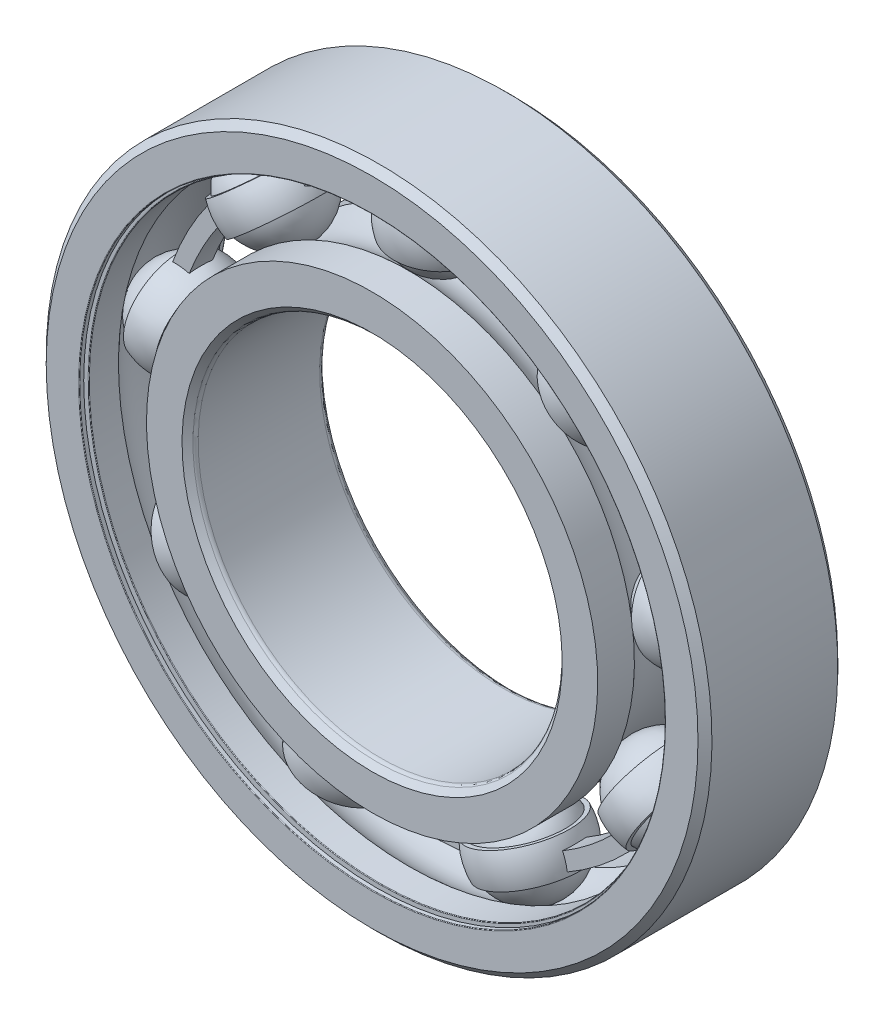
SolidWorks part; units mm, degrees
ref_plane "Front Plane" through (0, 0, 0) normal (0, 0, 1) x (1, 0, 0)
ref_plane "Top Plane" through (0, 0, 0) normal (0, 1, 0) x (1, 0, 0)
ref_plane "Right Plane" through (0, 0, 0) normal (1, 0, 0) x (0, 0, -1)
sketch "Sketch1" plane through (0, 0, 0) normal (0, 0, 1) x (1, 0, 0)
  line L0 (-50, 0) -> (50, 0) construction
  line L1 (-27.5, 0) -> (27.5, 0) construction
  circle A0 centre (0, 0) radius 27.5 construction
  circle A1 centre (0, 0) radius 50 construction
  point P3 (0, 0)
  point P6 (0, 0)
  point P7 (0, -27.5)
  point P11 (0, -50)
  point P12 (0, 27.5)
  point P13 (0, 50)
  dimension "OD" = 100
  dimension "ID" = 55
sketch "Sketch2" plane through (0, 0, 0) normal (1, 0, 0) x (0, 0, -1)
  line L0 (-10.5, 50) -> (10.5, 50) construction
  line L1 (0, 50) -> (0, -50) construction
  line L2 (9.45, 50) -> (-9.45, 50)
  line L3 (-9.45, 50) -> (-10.5, 48.95)
  line L4 (-10.5, 48.95) -> (-10.5, 43.6115)
  line L5 (-10.5, 43.6115) -> (-4.9875, 43.6115)
  line L6 (10.5, 43.6115) -> (4.9875, 43.6115)
  line L7 (10.5, 48.95) -> (10.5, 43.6115)
  line L8 (9.45, 50) -> (10.5, 48.95)
  line L9 (0, 50) -> (0, 38.75) construction
  line L10 (0, 38.75) -> (0, 27.5) construction
  line L11 (0, 50) -> (0, -50) construction
  line L12 (-10.5, 0) -> (10.5, 0) construction
  line L13 (10.5, 27.5) -> (-10.5, 27.5) construction
  line L14 (0, 45.7149) -> (0, 31.7851) construction
  line L15 (-10.5, -27.5) -> (10.5, -27.5) construction
  line L16 (-10.5, -27.5) -> (-10.5, 27.5) construction
  line L17 (10.5, 50) -> (10.5, -50) construction
  arc A0 (-4.9875, 43.6115) -> (4.9875, 43.6115) centre (0, 38.75) cw
  circle A1 centre (0, 38.75) radius 6.9649 construction
  point P14 (0, 27.5)
  point P17 (0, 0)
  point P21 (0, 50)
  point P29 (0, 27.5)
  point P30 (0, -27.5)
  point P35 (0, 45.7149)
  dimension "Approx. Ball Dia." = 13.9298
  dimension "Width" = 21
  dimension "D1" = 45
  dimension "D2" = 1.05
  dimension "D3" = 9.975
  dimension "D4" = 4.8615
  dimension "For Shaft Diameter" = 55
  dimension "For Housing ID" = 100
sketch "Sketch3" plane through (0, 0, 0) normal (1, 0, 0) x (0, 0, -1)
  line L0 (9.45, 50) -> (10.5, 48.95) construction
  line L1 (10.5, 48.95) -> (10.5, 43.6115) construction
  line L2 (10.5, 43.6115) -> (4.9875, 43.6115) construction
  line L3 (-10.5, 43.6115) -> (-4.9875, 43.6115) construction
  line L4 (-10.5, 48.95) -> (-10.5, 43.6115) construction
  line L5 (-9.45, 50) -> (-10.5, 48.95) construction
  line L6 (9.45, 50) -> (-9.45, 50) construction
  line L7 (9.45, 50) -> (10.5, 48.95)
  line L8 (10.5, 48.95) -> (10.5, 43.6115)
  line L9 (10.5, 43.6115) -> (4.9875, 43.6115)
  line L10 (-10.5, 43.6115) -> (-4.9875, 43.6115)
  line L11 (-10.5, 48.95) -> (-10.5, 43.6115)
  line L12 (-9.45, 50) -> (-10.5, 48.95)
  line L13 (9.45, 50) -> (-9.45, 50)
  arc A0 (4.9875, 43.6115) -> (-4.9875, 43.6115) centre (0, 38.75) ccw construction
  arc A1 (4.9875, 43.6115) -> (-4.9875, 43.6115) centre (0, 38.75) ccw
revolve "Revolve1" add sketch "Sketch3" angle 360 about L12
sketch "Sketch8" plane through (0, 0, 0) normal (1, 0, 0) x (0, 0, -1)
  line L0 (-10.5, 43.6115) -> (-4.9875, 43.6115) construction
  line L1 (-9.828, 43.6115) -> (-9.45, 43.6115)
  line L2 (-9.828, 43.6115) -> (-9.828, 45.741) construction
  line L3 (-9.828, 45.741) -> (-9.45, 45.741)
  line L4 (-9.45, 43.6115) -> (-9.45, 45.741)
  line L5 (10.5, 43.6115) -> (4.9875, 43.6115) construction
  line L6 (9.45, 43.6115) -> (9.828, 43.6115)
  line L7 (9.45, 43.6115) -> (9.45, 45.741)
  line L8 (9.45, 45.741) -> (9.828, 45.741)
  line L9 (9.828, 43.6115) -> (9.828, 45.741) construction
  line L10 (-9.45, 45.741) -> (9.45, 45.741) construction
  line L11 (0, 50) -> (0, -50) construction
  line L12 (-9.828, 45.741) -> (-9.828, 47.8705) construction
  line L13 (-9.828, 47.8705) -> (-9.828, 50) construction
  line L14 (-10.5, 50) -> (10.5, 50) construction
  line L15 (-9.828, 43.6115) -> (-10.5, 43.6115)
  line L16 (-10.5, 43.6115) -> (-10.5, 43.9895)
  line L17 (-10.5, 48.95) -> (-10.5, 43.6115) construction
  line L18 (-10.5, 43.9895) -> (-9.828, 43.9895)
  line L19 (-9.828, 43.9895) -> (-9.828, 45.741)
  line L20 (9.828, 43.6115) -> (10.5, 43.6115)
  line L21 (10.5, 43.6115) -> (10.5, 43.9895)
  line L22 (10.5, 48.95) -> (10.5, 43.6115) construction
  line L23 (10.5, 43.9895) -> (9.828, 43.9895)
  line L24 (9.828, 43.9895) -> (9.828, 45.741)
  point P12 (0, 45.741)
  dimension "D1" = 18.9
  dimension "D2" = 0.378
revolve "Cut-Revolve1" cut sketch "Sketch8" angle 360 about L12
sketch "Sketch4" plane through (0, 0, 0) normal (1, 0, 0) x (0, 0, -1)
  line L0 (0, 50) -> (0, -50) construction
  line L1 (0, 50) -> (0, -50) construction
  line L2 (-9.45, 27.5) -> (-10.5, 28.55)
  line L3 (-10.5, 28.55) -> (-10.5, 33.8885)
  line L5 (-10.5, 33.8885) -> (-4.9875, 33.8885)
  line L6 (-9.45, 27.5) -> (9.45, 27.5)
  line L8 (9.45, 27.5) -> (10.5, 28.55)
  line L10 (10.5, 28.55) -> (10.5, 33.8885)
  line L11 (10.5, 33.8885) -> (4.9875, 33.8885)
  line L12 (-10.5, 48.95) -> (-10.5, 43.6115) construction
  line L13 (9.45, 50) -> (10.5, 48.95) construction
  line L15 (10.5, -48.95) -> (10.5, 48.95) construction
  line L16 (9.45, 50) -> (9.45, -50) construction
  arc A1 (4.9875, 33.8885) -> (-4.9875, 33.8885) centre (0, 38.75) cw
  circle A2 centre (0, 38.75) radius 6.9649 construction
  point P1 (0, 27.5)
revolve "Revolve2" add sketch "Sketch4" angle 360 about L12
sketch "Sketch5" plane through (0, 0, 0) normal (1, 0, 0) x (0, 0, -1)
  line L0 (-6.9649, 38.75) -> (6.9649, 38.75)
  arc A2 (-6.9649, 38.75) -> (6.9649, 38.75) centre (0, 38.75) cw
  arc A3 (4.9875, 43.6115) -> (-4.9875, 43.6115) centre (0, 38.75) ccw construction
revolve "Revolve3" add sketch "Sketch5" angle 360 about L0
sketch "Sketch6" plane through (0, 0, 0) normal (1, 0, 0) x (0, 0, -1)
  line L0 (-4.9875, 43.6115) -> (-4.9875, 41.1808) construction
  line L1 (-4.9875, 41.1808) -> (-4.9875, 38.75) construction
  line L2 (-4.9875, 38.75) -> (-4.9875, 36.3192) construction
  line L3 (-4.9875, 36.3192) -> (-4.9875, 33.8885) construction
  line L4 (-10.5, 41.1808) -> (-9.8378, 41.1808) construction
  line L5 (-4.9875, 41.1808) -> (-4.9875, 36.3192) construction
  line L7 (-9.8378, 41.1808) -> (-9.1756, 41.1808) construction
  line L8 (-9.1756, 41.1808) -> (-8.5135, 41.1808) construction
  line L10 (0, 50) -> (0, -50) construction
  line L11 (0, 50) -> (0, -50) construction
  line L12 (-10.5, 43.6115) -> (-10.5, 41.1808) construction
  line L13 (-7.1891, 41.1808) -> (-6.5269, 41.1808) construction
  line L14 (-10.5, 48.95) -> (-10.5, -48.95) construction
  line L15 (-10.5, 41.1808) -> (-10.5, 38.75) construction
  line L16 (-10.5, 38.75) -> (-10.5, 36.3192) construction
  line L17 (-10.5, 36.3192) -> (-10.5, 33.8885) construction
  line L18 (-8.5135, 41.1808) -> (-7.8513, 41.1808) construction
  line L19 (-7.8513, 41.1808) -> (-7.1891, 41.1808) construction
  line L20 (-6.5269, 41.1808) -> (-7.1891, 41.1808)
  line L21 (-10.5, 36.3192) -> (-9.8378, 36.3192) construction
  line L22 (-9.8378, 36.3192) -> (-9.1756, 36.3192) construction
  line L23 (-9.1756, 36.3192) -> (-8.5135, 36.3192) construction
  line L24 (-8.5135, 36.3192) -> (-7.8513, 36.3192) construction
  line L25 (-7.8513, 36.3192) -> (-7.1891, 36.3192) construction
  line L26 (-7.1891, 36.3192) -> (-6.5269, 36.3192) construction
  line L27 (-6.5269, 36.3192) -> (-7.1891, 36.3192)
  line L28 (-7.8513, 41.1808) -> (-7.8513, 36.3192) construction
  line L30 (-7.5202, 41.1808) -> (-7.5202, 36.3192) construction
  circle A0 centre (0, 38.75) radius 6.9649 construction
  arc A2 (-7.1891, 36.3192) -> (-7.1891, 41.1808) centre (1.5684, 38.75) cw
  arc A3 (-6.5269, 41.1808) -> (-6.5269, 36.3192) centre (0, 38.75) ccw
revolve "Revolve4" add sketch "Sketch6" angle 360 about L11
sketch "Sketch7" plane through (0, 0, 0) normal (0, 0, 1) x (1, 0, 0)
  line L0 (-6.9649, 38.75) -> (6.9649, 38.75) construction
  line L1 (0, 31.7851) -> (0, 45.7149) construction
  line L2 (0, 0) -> (13.2533, 36.4131) construction
  line L8 (0, 50) -> (0, -50) construction
  line L9 (24.908, 29.6842) -> (26.4705, 31.5463)
  line L10 (0, 50) -> (0, -50) construction
  line L11 (0, 41.1808) -> (0, 38.75)
  arc A1 (24.908, 29.6842) -> (0, 38.75) centre (0, 0) ccw
  arc A2 (26.4705, 31.5463) -> (0, 41.1808) centre (0, 0) ccw
  dimension "D1" = 40
  dimension "D2" = 13.9298
extrude "Boss-Extrude1" add sketch "Sketch7" along normal mid plane 3.5
pattern_circular "CirPattern1" count 9 over 360 about axis through (0, 0, 10.5) along (0, 0, -1) of bodies 104 134
pattern_circular "CirPattern2" count 9 over 360 about axis through (0, 0, 10.5) along (0, 0, -1) of "Revolve4", "Boss-Extrude1" reverse direction yes
fillet "Fillet1" radius 0.0945 4 edges at (0, -43.6115, -9.45) (0, -43.9895, -10.5) (0, -43.6115, 9.45) (0, -43.9895, 10.5)
fillet "Fillet2" radius 0.7875 2 edges at (0, -27.5, -9.45) (0, -27.5, 9.45)
ref_plane "Plane1" through (13.2533, 36.4131, 0) normal (0.342, 0.9397, 0) x (0.9397, -0.342, 0)
sketch "Sketch9" plane through (13.2533, 36.4131, 0) normal (0.342, 0.9397, 0) x (0.9397, -0.342, 0)
  line L0 (-6.7084, -1.75) -> (-6.7084, -5.25)
  line L1 (-6.7084, -5.25) -> (-2.9099, -5.25)
  line L2 (-2.9099, -5.25) -> (0, -2.8083)
  line L3 (0, -2.8083) -> (2.9099, -5.25)
  line L4 (2.9099, -5.25) -> (6.7084, -5.25)
  line L5 (6.7084, -5.25) -> (6.7084, -1.75)
  line L6 (6.7084, -1.75) -> (-6.7084, -1.75)
  line L7 (0, -1.75) -> (0, 0) construction
  line L8 (-6.7084, -1.75) -> (-6.7084, 0) construction
  dimension "D1" = 3.5
  dimension "D2" = 1.75
  dimension "D3" = 40
extrude "Boss-Extrude2" [suppressed] add sketch "Sketch9" along normal blind 6.0943 draft 15 and the other way blind 6.0943 draft 10 separate body draft outward yes other way draft outward yes
fillet "Fillet3" [suppressed] radius 1.05
mirror "Mirror1" [suppressed] about plane through (0, 0, 0) normal (0, 0, 1) of bodies 149
pattern_circular "CirPattern3" [suppressed] count 9 over 360 about axis through (0, 0, 10.5) along (0, 0, -1) of bodies 158 149
equation "\"D2@Sketch2\" = \"Width@Sketch2\" * .05"
equation "\"D3@Sketch2\"=\"Width@Sketch2\" * .475"
equation "\"D4@Sketch2\" =  (  (  ( \"OD@Sketch1\" - \"Width@Sketch2\" )  / 2 )  / 3.25 )  / 2.5"
equation "\"D1@Boss-Extrude1\" = \"Width@Sketch2\" / 6"
equation "\"D1@Sketch8\"=\"Width@Sketch2\"*.9"
equation "\"D2@Sketch8\"=\"D1@Sketch8\"*.02"
equation "\"D1@Fillet1\" = \"D2@Sketch8\" * .25"
equation "\"D1@Fillet2\" = \"D2@Sketch2\" * .75"
equation "\"Approx No of Balls@CirPattern1\" = ( pi * \"OD@Sketch1\" ) * .4 / \"Approx. Ball Dia.@Sketch2\""
equation "\"D1@Sketch7\" = 360 / \"Approx No of Balls@CirPattern1\""
equation "\"D1@CirPattern2\" = \"Approx No of Balls@CirPattern1\""
equation "\"D2@Sketch7\"=\"Approx. Ball Dia.@Sketch2\""
equation "\"D2@Sketch9\" = \"D1@Boss-Extrude1\" * .5"
equation "\"D1@Sketch9\"=\"D2@Sketch9\"*2"
equation "\"D1@Boss-Extrude2\"=\"Approx. Ball Dia.@Sketch2\"*.4375"
equation "\"D2@Boss-Extrude2\"=\"D1@Boss-Extrude2\""
equation "\"D1@CirPattern3\" = \"Approx No of Balls@CirPattern1\""
equation "\"D1@Fillet3\"=\"D1@Sketch9\" * .3"
